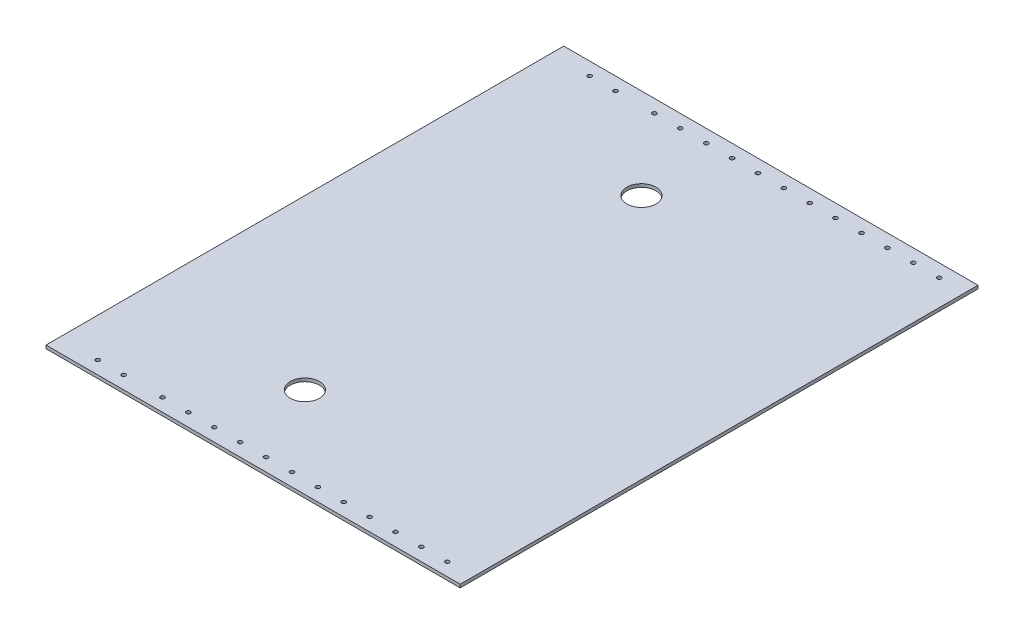
SolidWorks part; units mm, degrees
material "Lexan"
ref_plane "Front Plane" through (0, 0, 0) normal (0, 0, 1) x (1, 0, 0)
ref_plane "Top Plane" through (0, 0, 0) normal (0, 1, 0) x (1, 0, 0)
ref_plane "Right Plane" through (0, 0, 0) normal (1, 0, 0) x (0, 0, -1)
sketch "Sketch1" plane through (0, 0, 0) normal (0, 1, 0) x (1, 0, 0)
  line L1 (0, 0) -> (571.5, 0)
  line L2 (0, 0) -> (0, 508)
  line L3 (0, 508) -> (571.5, 508)
  line L4 (571.5, 0) -> (571.5, 508)
  dimension "D1" = 571.5
  dimension "D2" = 508
extrude "Boss-Extrude1" add sketch "Sketch1" along normal blind 3.175
sketch "Sketch2" plane through (0, 3.175, 0) normal (0, 1, 0) x (1, 0, 0)
  line L0 (273.05, 419.1) -> (273.05, 508) construction
  line L1 (215.9, 419.1) -> (330.2, 419.1) construction
  line L3 (215.9, 88.9) -> (330.2, 88.9) construction
  line L4 (571.5, 0) -> (571.5, 508) construction
  line L5 (571.5, 508) -> (0, 508) construction
  line L6 (273.05, 88.9) -> (273.05, 0) construction
  line L7 (0, 0) -> (571.5, 0) construction
  circle A1 centre (330.2, 419.1) radius 14.2875
  circle A3 centre (330.2, 88.9) radius 14.2875
  point P1 (0, 0)
  dimension "D1" = 114.3
  dimension "D2" = 28.575
  dimension "D3" = 241.3
  dimension "D4" = 28.575
  dimension "D7" = 330.2
  dimension "D8" = 241.3
extrude "Cut-Extrude1" cut sketch "Sketch2" against normal blind 3.175
sketch "Sketch4" plane through (0, 3.175, 0) normal (0, 1, 0) x (1, 0, 0)
  line L0 (571.5, 495.3) -> (0, 495.3) construction
  line L1 (571.5, 0) -> (571.5, 508) construction
  line L2 (0, 508) -> (0, 0) construction
  line L3 (571.5, 508) -> (0, 508) construction
  line L4 (0, 254) -> (571.5, 254) construction
  line L5 (571.5, 12.7) -> (0, 12.7) construction
  circle A0 centre (546.1, 495.3) radius 2.0193
  circle A1 centre (520.7, 495.3) radius 2.0193
  circle A2 centre (495.3, 495.3) radius 2.0193
  circle A3 centre (469.9, 495.3) radius 2.0193
  circle A4 centre (444.5, 495.3) radius 2.0193
  circle A5 centre (419.1, 495.3) radius 2.0193
  circle A6 centre (393.7, 495.3) radius 2.0193
  circle A7 centre (368.3, 495.3) radius 2.0193
  circle A8 centre (342.9, 495.3) radius 2.0193
  circle A9 centre (317.5, 495.3) radius 2.0193
  circle A10 centre (292.1, 495.3) radius 2.0193
  circle A11 centre (266.7, 495.3) radius 2.0193
  circle A12 centre (228.6, 495.3) radius 2.0193
  circle A13 centre (203.2, 495.3) radius 2.0193
  circle A14 centre (203.2, 12.7) radius 2.0193
  circle A15 centre (228.6, 12.7) radius 2.0193
  circle A16 centre (266.7, 12.7) radius 2.0193
  circle A17 centre (292.1, 12.7) radius 2.0193
  circle A18 centre (317.5, 12.7) radius 2.0193
  circle A19 centre (342.9, 12.7) radius 2.0193
  circle A20 centre (368.3, 12.7) radius 2.0193
  circle A21 centre (393.7, 12.7) radius 2.0193
  circle A22 centre (419.1, 12.7) radius 2.0193
  circle A23 centre (444.5, 12.7) radius 2.0193
  circle A24 centre (469.9, 12.7) radius 2.0193
  circle A25 centre (495.3, 12.7) radius 2.0193
  circle A26 centre (520.7, 12.7) radius 2.0193
  circle A27 centre (546.1, 12.7) radius 2.0193
  dimension "D2" = 4.0386
  dimension "D3" = 25.4
  dimension "D5" = 38.1
  dimension "D6" = 25.4
  dimension "D1" = 12.7
  dimension "D4" = 12
extrude "Cut-Extrude3" cut sketch "Sketch4" against normal through all both
sketch "Sketch5" plane through (0, 0, 0) normal (-1, 0, 0) x (0, 0, 1)
  line L1 (-567.431, 71.2281) -> (52.1486, 71.2281)
  line L2 (-567.431, 71.2281) -> (-567.431, -17.807)
  line L3 (-567.431, -17.807) -> (52.1486, -17.807)
  line L4 (52.1486, 71.2281) -> (52.1486, -17.807)
extrude "Cut-Extrude4" cut sketch "Sketch5" against normal blind 165.1
